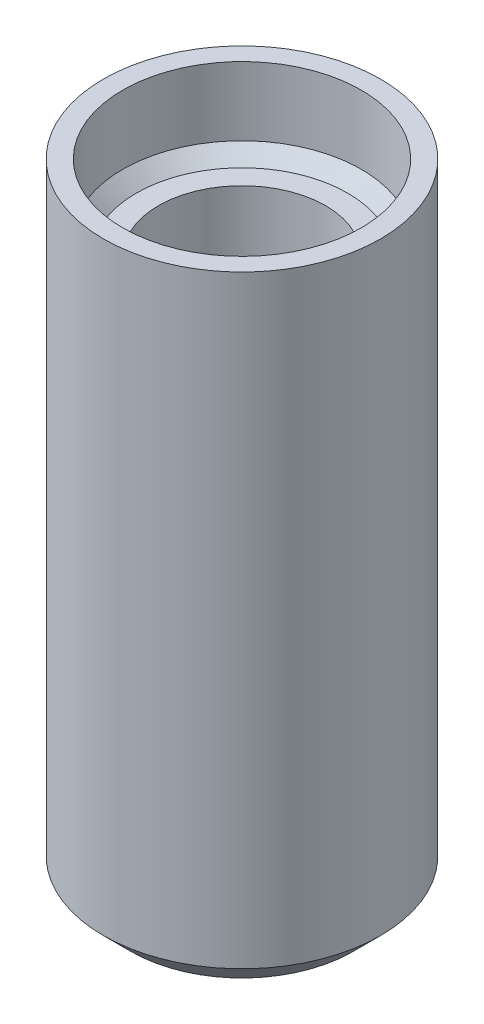
SolidWorks part; units mm, degrees
ref_plane "Front Plane" through (0, 0, 0) normal (0, 0, 1) x (1, 0, 0)
ref_plane "Top Plane" through (0, 0, 0) normal (0, 1, 0) x (1, 0, 0)
ref_plane "Right Plane" through (0, 0, 0) normal (1, 0, 0) x (0, 0, -1)
sketch "Sketch1" plane through (0, 0, 0) normal (0, 1, 0) x (1, 0, 0)
  line L0 (-2.5652, -1.65) -> (2.5652, -1.65)
  circle A0 centre (0, 0) radius 3.05
  circle A1 centre (0, 0) radius 5.05
  dimension "D1" = 6.1
  dimension "D3" = 1.65
  dimension "D2" = 2
extrude "Boss-Extrude1" add sketch "Sketch1" along normal blind 20 contours A1 A0 | L0 A0 region at (0, 0, 2.2227) region at (-4.9072, 0, 0)
sketch "Sketch2" plane through (0, 0, 0) normal (0, -1, 0) x (1, 0, 0)
  circle A1 centre (0, 0) radius 5.05
  circle A2 centre (0, 0) radius 5.05
  dimension "D1" = 0
extrude "Boss-Extrude2" add sketch "Sketch2" against normal blind 2
sketch "Sketch4" plane through (0, 20, 0) normal (0, 1, 0) x (1, 0, 0)
  circle A0 centre (0, 0) radius 4.35
  circle A1 centre (0, 0) radius 5.05
  circle A2 centre (0, 0) radius 5.05
  dimension "D1" = 0
  dimension "D2" = 0.7
extrude "Boss-Extrude3" add sketch "Sketch4" along normal blind 3
chamfer "Chamfer1" distance 1 angle 45 1 edges at (0, 0, 5.05)
chamfer "Chamfer2" distance 0.5 angle 45 1 edges at (0, 20, 4.35)
sketch "Sketch5" plane through (0, 0, 0) normal (0, -1, 0) x (1, 0, 0)
  line L0 (-1.326, 0) -> (1.326, 0) construction
  line L1 (-3.5217, -2) -> (3.5217, -2) construction
  circle A0 centre (0, 0) radius 4.05 construction
  text T0 "<b>0</b>" font "Calibri" height in points 16
  dimension "D1" = 2
extrude "Cut-Extrude1" cut sketch "Sketch5" against normal blind 0.4
extrude "Boss-Extrude4" add sketch "Sketch5<2>" against normal blind 0.4 separate body
sketch "Sketch5<2>" plane through (0, 0, 0) normal (0, -1, 0) x (1, 0, 0) same geometry as "Sketch5"
equation "\"ID\"= 6.3"
equation "\"notch\"= 6.3 / 2 - 1.5"
equation "\"D3@Sketch1\"=\"notch\""
